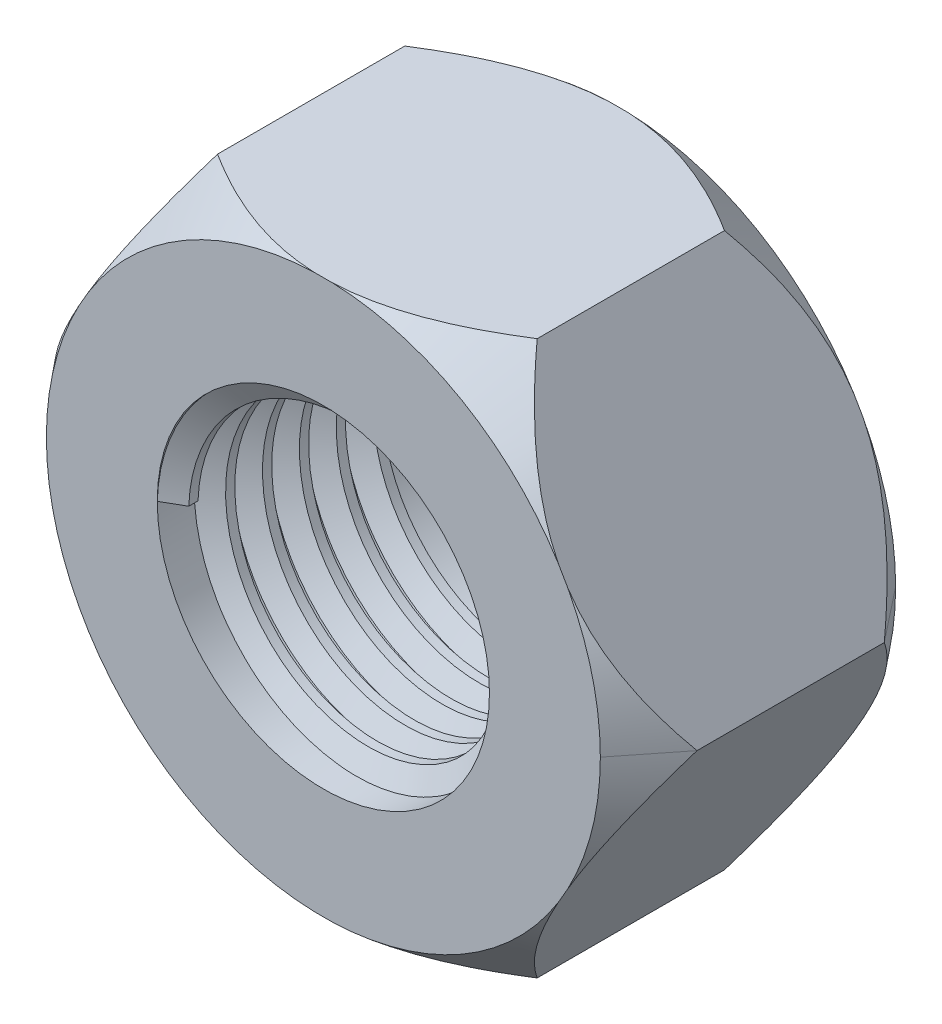
SolidWorks part; units mm, degrees
ref_plane "Front Plane" through (0, 0, 0) normal (0, 0, 1) x (1, 0, 0)
ref_plane "Top Plane" through (0, 0, 0) normal (0, 1, 0) x (1, 0, 0)
ref_plane "Right Plane" through (0, 0, 0) normal (1, 0, 0) x (0, 0, -1)
sketch "Sketch1" plane through (0, 0, 0) normal (0, 0, 1) x (1, 0, 0)
  line L1 (17.3205, 0) -> (8.6603, 15)
  line L2 (8.6603, 15) -> (-8.6603, 15)
  line L3 (-8.6603, 15) -> (-17.3205, 0)
  line L4 (-17.3205, 0) -> (-8.6603, -15)
  line L5 (-8.6603, -15) -> (8.6603, -15)
  line L6 (8.6603, -15) -> (17.3205, 0)
  circle A0 centre (0, 0) radius 15 construction
  circle A1 centre (0, 0) radius 9
  dimension "D2" = 18
  dimension "D1" = 30
extrude "Boss-Extrude1" add sketch "Sketch1" along normal blind 16
thread "Thread1" pitch 2 method extrude profile "Thread Profile1" start angle 0, offset 0, length 10, pitch 2, diameter 18
ref_plane "Plane1" through (-9, 0, 16) normal (0, -1, 0) x (-1, 0, 0)
sketch "Thread Profile1" plane through (-9, 0, 16) normal (0, -1, 0) x (-1, 0, 0)
  line L0 (0, 0) -> (0, 2) construction
  line L11 (0, 0) -> (0, 1.75)
  line L12 (0, 1.75) -> (-1.0825, 1.125)
  line L13 (-1.0825, 1.125) -> (-1.0825, 0.625)
  line L15 (-1.0825, 0.625) -> (0, 0)
  line L17 (-1.0825, 0.875) -> (0, 0.875) construction
  point P2 (0, 0)
  dimension "Pitch" = 2
  dimension "Profile_Angle" = 60
  dimension "Profile_Land" = 0.5
  dimension "Profile_Height" = 1.0825
sketch "Sketch4" plane through (0, 0, 16) normal (0, 0, 1) x (1, 0, 0)
  circle A0 centre (0, 0) radius 15
sketch "Sketch5" plane through (0, 0, 0) normal (0, 1, 0) x (1, 0, 0)
  line L0 (17.3205, -16) -> (15.0085, -16)
  line L1 (17.3205, -16) -> (17.3205, -13.0738)
  line L2 (17.3205, -13.0738) -> (15.0085, -16)
sweep "Cut-Sweep1" cut profiles "Sketch5" path "Sketch4"
ref_plane "Plane2" through (0, 0, 8) normal (0, 0, 1) x (1, 0, 0)
mirror "Mirror1" about plane through (0, 0, 8) normal (0, 0, 1) of "Cut-Sweep1"
